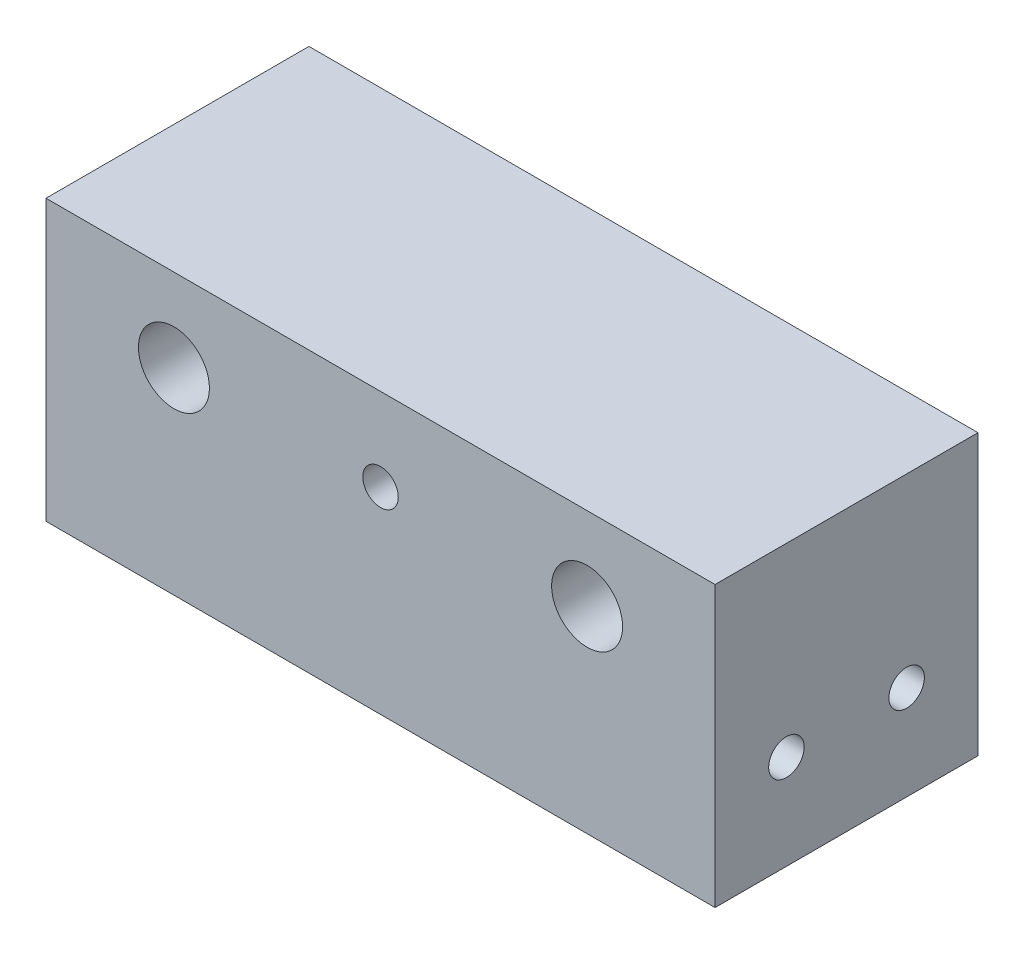
SolidWorks part; units mm, degrees
material "ABS"
ref_plane "X-Y Datum" through (0, 0, 0) normal (0, 0, 1) x (1, 0, 0)
ref_plane "X-Z Datum" through (0, 0, 0) normal (0, 1, 0) x (1, 0, 0)
ref_plane "Y-Z Datum" through (0, 0, 0) normal (1, 0, 0) x (0, 0, -1)
sketch "Sketch1" plane through (0, 0, 0) normal (0, 0, 1) x (1, 0, 0)
  line L1 (-28.275, 11.1125) -> (28.275, 11.1125)
  line L2 (-28.275, 11.1125) -> (-28.275, -11.1125)
  line L3 (-28.275, -11.1125) -> (28.275, -11.1125)
  line L4 (28.275, 11.1125) -> (28.275, -11.1125)
  line L5 (-28.275, 11.1125) -> (28.275, -11.1125) construction
  line L6 (-28.275, -11.1125) -> (28.275, 11.1125) construction
  point P0 (0, 0)
  dimension "D1" = 56.55
  dimension "D2" = 22.225
extrude "Boss-Extrude1" add sketch "Sketch1" along normal blind 22.225 contours L2 L3 L4 L1
sketch "Sketch2" plane through (0, 0, 22.225) normal (0, 0, 1) x (1, 0, 0)
  line L0 (-23.5453, 4.1125) -> (31.0951, 4.1125) construction
  line L1 (0, 11.1125) -> (0, -11.1125) construction
  line L2 (-28.275, 11.1125) -> (28.275, 11.1125) construction
  line L3 (-17.4625, 4.1125) -> (17.4625, 4.1125) construction
  line L4 (-28.275, -11.1125) -> (28.275, -11.1125) construction
  circle A0 centre (17.4625, 4.1125) radius 3
  circle A1 centre (-17.4625, 4.1125) radius 3
  circle A2 centre (0, 4.1125) radius 1.5
  point P10 (0, 4.1125)
  dimension "D1" = 6
  dimension "D4" = 3
  dimension "D2" = 34.925
  dimension "D3" = 7
extrude "Cut-Extrude1" cut sketch "Sketch2" against normal blind 10 contours A1 L0 L3 | L0 A1 L3 | L0 L3 A0 | L3 L0 A0 | A2 region at (17.4625, 4.1125, 22.225) region at (-17.4625, 4.1125, 22.225) region at (0, 4.1125, 22.225)
sketch "Sketch3" plane through (-28.275, 0, 0) normal (-1, 0, 0) x (0, 0, 1)
  line L0 (0, -4.5375) -> (22.225, -4.5375) construction
  line L1 (0, 11.1125) -> (0, -11.1125) construction
  line L2 (22.225, 184.8875) -> (22.225, -15.7125) construction
  line L3 (16.1925, -4.5375) -> (6.0325, -4.5375) construction
  line L4 (11.1125, 11.1125) -> (11.1125, -11.1125) construction
  line L5 (22.225, 11.1125) -> (0, 11.1125) construction
  line L6 (22.225, -11.1125) -> (0, -11.1125) construction
  line L7 (-277.475, -12.5375) -> (22.225, -12.5375) construction
  circle A0 centre (16.1925, -4.5375) radius 1.5
  circle A1 centre (6.0325, -4.5375) radius 1.5
  point P10 (11.1125, -4.5375)
  dimension "D1" = 3
  dimension "D2" = 10.16
  dimension "D3" = 8
extrude "Cut-Extrude2" cut sketch "Sketch3" against normal blind 10
sketch "Sketch5" plane through (0, -11.1125, 0) normal (0, -1, 0) x (1, 0, 0)
  line L4 (-28.275, 0) -> (28.275, 0)
  line L5 (28.275, 0) -> (28.275, 22.225)
  line L6 (28.275, 22.225) -> (-28.275, 22.225)
  line L7 (-28.275, 22.225) -> (-28.275, 0)
  line L8 (-28.275, 0) -> (28.275, 0)
  line L9 (28.275, 0) -> (28.275, 22.225)
  line L10 (28.275, 22.225) -> (-28.275, 22.225)
  line L11 (-28.275, 22.225) -> (-28.275, 0)
  dimension "D1" = 0
extrude "Boss-Extrude2" add sketch "Sketch5" along normal blind 1.4249
sketch "Sketch6" plane through (0, 0, 0) normal (0, 0, -1) x (-1, 0, 0)
  circle A0 centre (0, 0) radius 3.025
  dimension "D1" = 6.05
extrude "Cut-Extrude3" cut sketch "Sketch6" against normal blind 8
mirror "Mirror2" about plane through (0, 0, 0) normal (1, 0, 0) of "Cut-Extrude2"
